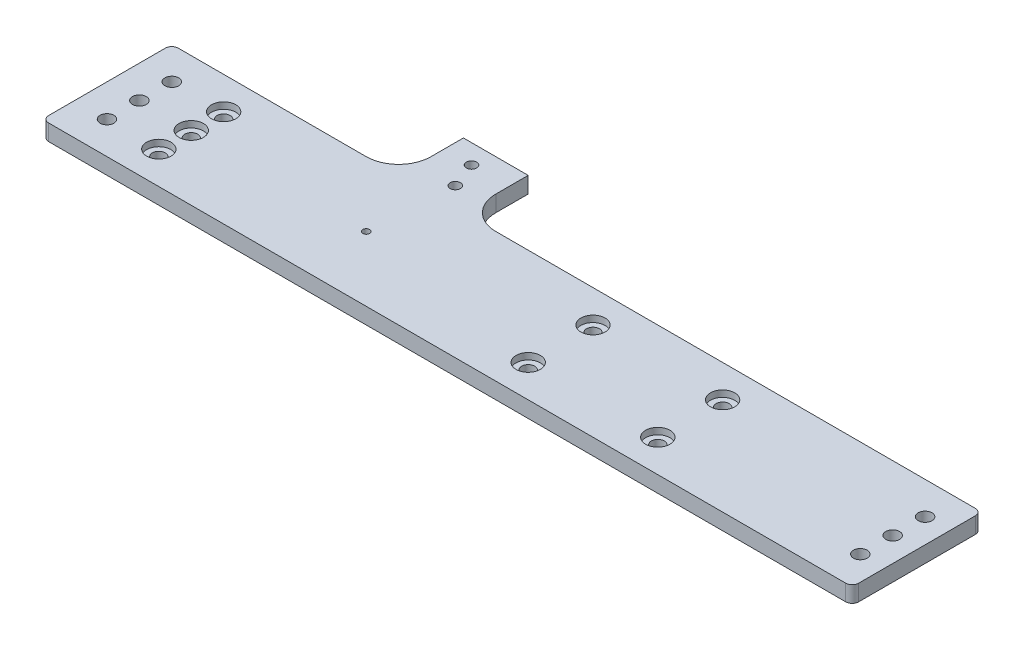
SolidWorks part; units mm, degrees
material "6061-T6 (SS)"
ref_plane "Front" through (0, 0, 0) normal (0, 0, 1) x (1, 0, 0)
ref_plane "Top" through (0, 0, 0) normal (0, 1, 0) x (1, 0, 0)
ref_plane "Right" through (0, 0, 0) normal (1, 0, 0) x (0, 0, -1)
sketch "Sketch1" plane through (0, 0, 0) normal (0, 1, 0) x (1, 0, 0)
  line L1 (-158.75, -25.4) -> (158.75, -25.4)
  line L2 (-158.75, -25.4) -> (-158.75, 25.4)
  line L3 (-158.75, 25.4) -> (158.75, 25.4)
  line L4 (158.75, -25.4) -> (158.75, 25.4)
  line L5 (-158.75, -25.4) -> (158.75, 25.4) construction
  line L6 (-158.75, 25.4) -> (158.75, -25.4) construction
  point P0 (0, 0)
  dimension "D1" = 50.8
  dimension "D2" = 317.5
extrude "Boss-Extrude1" add sketch "Sketch1" along normal blind 6.35
hole_wizard "CBORE for #10 Socket Head Cap Screw1" positions "Sketch2" profile "Sketch4" counterbore size "#10" standard "ANSI Inch" end condition through all
sketch "Sketch2" plane through (0, 6.35, 0) normal (0, 1, 0) x (1, 0, 0)
  line L2 (158.75, 25.4) -> (-158.75, 25.4) construction
  line L6 (-158.75, -25.4) -> (158.75, -25.4) construction
  line L8 (-158.75, 25.4) -> (-158.75, -25.4) construction
  line L12 (158.75, -25.4) -> (158.75, 25.4) construction
  line L15 (19.05, 12.7) -> (19.05, 25.4) construction
  line L17 (19.05, -12.7) -> (19.05, -25.4) construction
  line L18 (-125.73, -25.4) -> (-125.73, -12.7) construction
  line L20 (-125.73, 0) -> (-125.73, 12.7) construction
  line L21 (-125.73, 12.7) -> (-125.73, 25.4) construction
  line L22 (-125.73, 0) -> (-125.73, -12.7) construction
  point P64 (19.05, 12.7)
  point P66 (69.85, 12.7)
  point P68 (19.05, -12.7)
  point P70 (69.85, -12.7)
  point P92 (-125.73, 12.7)
  point P94 (-125.73, 0)
  point P102 (-125.73, -12.7)
  dimension "D2" = 50.8
  dimension "D3" = 25.4
  dimension "D4" = 88.9
  dimension "D5" = 33.02
sketch "Sketch4" plane through (-125.73, 6.35, 12.7) normal (1, 0, 0) x (0, 0, 1)
  line L0 (0, 0) -> (0, 6.35)
  line L1 (0, 6.35) -> (2.5527, 6.35)
  line L3 (2.5527, 6.35) -> (2.5527, 2.54)
  line L4 (2.5527, 2.54) -> (4.7625, 2.54)
  line L5 (4.7625, 2.54) -> (4.7625, 0)
  line L7 (4.7625, 0) -> (0, 0)
  line L11 (0, -6.35) -> (0, 107.95) construction
  dimension "Thru Hole Dia." = 5.1054
  dimension "Thru Hole Depth" = 6.35
  dimension "C'Bore Dia." = 9.525
  dimension "C'Bore Depth" = 2.54
sketch "Sketch7" plane through (0, 0, 0) normal (0, -1, 0) x (1, 0, 0)
  line L0 (-146.05, 25.4) -> (-146.05, 12.7) construction
  line L1 (-158.75, 25.4) -> (158.75, 25.4) construction
  line L2 (-146.05, 12.7) -> (-146.05, 0) construction
  line L3 (-146.05, 0) -> (-146.05, -12.7) construction
  line L4 (-146.05, -12.7) -> (-146.05, -25.4) construction
  line L5 (158.75, -25.4) -> (-158.75, -25.4) construction
  line L7 (-158.75, -25.4) -> (-158.75, 25.4) construction
  line L8 (149.225, 25.4) -> (149.225, 12.7) construction
  line L9 (149.225, 12.7) -> (149.225, 0) construction
  line L10 (149.225, 0) -> (149.225, -12.7) construction
  line L11 (149.225, -12.7) -> (149.225, -25.4) construction
  line L13 (158.75, 25.4) -> (158.75, -25.4) construction
  point P0 (-146.05, 12.7)
  point P2 (-146.05, 0)
  point P4 (-146.05, -12.7)
  point P6 (149.225, 12.7)
  point P8 (149.225, 0)
  point P10 (149.225, -12.7)
  dimension "D1" = 12.7
  dimension "D2" = 9.525
hole_wizard "1/4-28 Tapped Hole1" positions "Sketch7" profile "Sketch6" tap size "1/4-28" standard "ANSI Inch" end condition through all
sketch "Sketch6" plane through (-146.05, 0, 12.7) normal (1, 0, 0) x (0, 0, -1)
  line L0 (0, 0) -> (0, 6.35)
  line L1 (0, 6.35) -> (2.7051, 6.35)
  line L2 (2.7051, 6.35) -> (2.7051, 0)
  line L5 (2.7051, 0) -> (0, 0)
  line L11 (0, -6.35) -> (0, 107.95) construction
  dimension "Thru Tap Drill Dia." = 5.4102
  dimension "Thru Tap Drill Depth" = 6.35
sketch "Sketch10" plane through (0, 0, 0) normal (0, -1, 0) x (-1, 0, 0)
  line L0 (158.75, 25.4) -> (158.75, -25.4) construction
  point P0 (57.15, 0)
  dimension "D1" = 101.6
hole_wizard "#6-32 Tapped Hole1" positions "Sketch10" profile "Sketch9" tap size "#6-32" standard "ANSI Inch" end condition through all
sketch "Sketch9" plane through (-57.15, 0, 0) normal (1, 0, 0) x (0, 0, -1)
  line L0 (0, 0) -> (0, 6.35)
  line L1 (0, 6.35) -> (1.3525, 6.35)
  line L2 (1.3525, 6.35) -> (1.3525, 0)
  line L5 (1.3525, 0) -> (0, 0)
  line L11 (0, -6.35) -> (0, 107.95) construction
  dimension "Thru Tap Drill Dia." = 2.7051
  dimension "Thru Tap Drill Depth" = 6.35
cosmetic thread "Hole Thread1" parameters "D2"=3.5052
sketch "Sketch11" plane through (0, 0, 0) normal (0, -1, 0) x (1, 0, 0)
  line L0 (158.75, -25.4) -> (-158.75, -25.4) construction
  line L1 (-70.0118, -25.4) -> (-48.1024, -25.4)
  line L2 (-70.0118, -25.4) -> (-70.0118, -45.81)
  line L3 (-70.0118, -45.81) -> (-48.1024, -45.81)
  line L4 (-48.1024, -25.4) -> (-48.1024, -45.81)
extrude "Boss-Extrude2" [suppressed] add sketch "Sketch11" against normal up to surface (6.35 mm away) up to face at (-57.15, 6.35, -1.3526)
sketch "Sketch12" plane through (0, 6.35, 0) normal (0, 1, 0) x (1, 0, 0)
  line L5 (-158.75, 25.4) -> (-158.75, -25.4) construction
  line L6 (-69.85, 25.4) -> (-69.85, 50.8)
  line L7 (158.75, 25.4) -> (-158.75, 25.4) construction
  line L8 (-69.85, 50.8) -> (-44.45, 50.8)
  line L9 (-44.45, 50.8) -> (-44.45, 25.4)
  line L10 (-69.85, 25.4) -> (-44.45, 25.4)
  dimension "D4" = 88.9
  dimension "D5" = 25.4
  dimension "D6" = 25.4
extrude "Boss-Extrude3" add sketch "Sketch12" against normal up to surface (6.35 mm away) up to face at (-57.15, 0, -1.3526)
sketch "Sketch15" plane through (0, 0, 0) normal (0, -1, 0) x (-1, 0, 0)
  point P0 (59.055, 43.18)
  point P3 (55.245, 33.02)
hole_wizard "#10-32 Tapped Hole1" positions "Sketch15" profile "Sketch14" tap size "#10-32" standard "ANSI Inch" end condition through all
sketch "Sketch14" plane through (-59.055, 0, -43.18) normal (1, 0, 0) x (0, 0, -1)
  line L0 (0, 0) -> (0, 6.35)
  line L1 (0, 6.35) -> (2.0193, 6.35)
  line L2 (2.0193, 6.35) -> (2.0193, 0)
  line L5 (2.0193, 0) -> (0, 0)
  line L11 (0, -6.35) -> (0, 107.95) construction
  dimension "Thru Tap Drill Dia." = 4.0386
  dimension "Thru Tap Drill Depth" = 6.35
fillet "Fillet1" radius 12.7 2 edges at (-44.45, 3.175, -25.4) (-69.85, 3.175, -25.4)
fillet "Fillet2" radius 2.54 4 edges at (158.75, 3.175, -25.4) (158.75, 3.175, 25.4) (-158.75, 3.175, 25.4) (-158.75, 3.175, -25.4)
